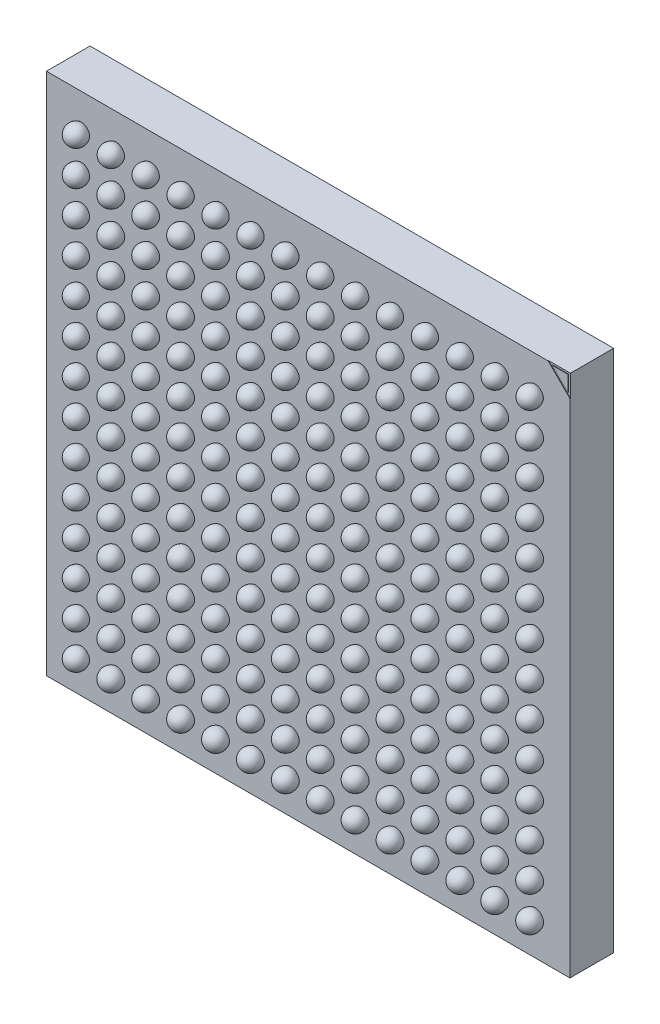
SolidWorks part; units mm, degrees
ref_plane "Front Plane" through (0, 0, 0) normal (0, 0, 1) x (1, 0, 0)
ref_plane "Top Plane" through (0, 0, 0) normal (0, 1, 0) x (1, 0, 0)
ref_plane "Right Plane" through (0, 0, 0) normal (1, 0, 0) x (0, 0, -1)
sketch "Sketch1" plane through (0, 0, 0) normal (0, 0, 1) x (1, 0, 0)
  line L1 (-6, 6) -> (6, 6)
  line L2 (-6, 6) -> (-6, -6)
  line L3 (-6, -6) -> (6, -6)
  line L4 (6, 6) -> (6, -6)
  line L5 (-6, 6) -> (6, -6) construction
  line L6 (-6, -6) -> (6, 6) construction
  point P0 (0, 0)
  dimension "D1" = 12
  dimension "D2" = 12
extrude "Boss-Extrude1" add sketch "Sketch1" along normal blind 1
sketch3d "3DSketch2" plane through (0, 0, 0) normal (0, 0, 1) x (1, 0, 0)
  dimension "D1" = 0.12
sketch3d "3DSketch1" plane through (0, 0, 0) normal (0, 0, 1) x (1, 0, 0)
  dimension "D1" = 0.01
sketch "Sketch3" plane through (0, 0, 1.12) normal (0, 0, 1) x (1, 0, 0)
  line L0 (-5.2, 5.425) -> (-5.2, 4.975)
  arc A0 (-5.2, 5.425) -> (-5.2, 4.975) centre (-5.2, 5.2) ccw
  dimension "D2" = 0.225
  dimension "D1" = 5.2
  dimension "D3" = 5.2
revolve "Revolve1" add sketch "Sketch3" angle 360 about L0
pattern_linear "LPattern1" count 14 spacing 0.8 along (1, 0, 0) of "Revolve1"
pattern_linear "LPattern2" count 14 spacing 0.8 along (0, -1, 0) of "Revolve1"
sketch "Sketch4" plane through (0, 0, 1) normal (0, 0, 1) x (1, 0, 0)
  line L0 (-6, -6) -> (6, 6) construction
sketch "Sketch5" plane through (0, 0, 1.12) normal (0, 0, 1) x (1, 0, 0)
  line L0 (5.2, 5.2) -> (5.2, -5.2) construction
  line L1 (-6, -6) -> (6, 6) construction
  line L2 (5.2, 4.63) -> (5.2, 4.17)
  arc A0 (5.2, 4.63) -> (5.2, 4.17) centre (5.2, 4.4) ccw
  dimension "D2" = 0.23
  dimension "D1" = 0.8
revolve "Revolve2" add sketch "Sketch5" angle 360 about L0
pattern_linear "LPattern3" count 12 spacing 0.8 along (0, -1, 0) of "Revolve2"
sketch "Sketch8" plane through (0, 0, 1.12) normal (0, 0, 1) x (1, 0, 0)
  line L0 (5.2, -4.9726) -> (5.2, -5.4326)
  line L1 (-5.2026, -5.2026) -> (6.4563, -5.2026) construction
  line L2 (-6, -6) -> (6, 6) construction
  line L3 (5.2, 5.2) -> (5.2, -5.8448) construction
  arc A0 (5.2, -4.9726) -> (5.2, -5.4326) centre (5.2, -5.2026) cw
  dimension "D2" = 0.23
  dimension "D1" = 0
  dimension "D3" = 0
revolve "Revolve3" add sketch "Sketch8" angle 360 about L0
pattern_linear "LPattern4" count 13 spacing 0.8 along (-1, 0, 0) of "Revolve3"
sketch "Sketch9" plane through (0, 0, 1.12) normal (0, 0, 1) x (1, 0, 0)
  line L0 (-5.2, 4.4) -> (-4.4, 4.4) construction
  line L1 (-4.4, 4.4) -> (-4.4, 5.2) construction
  line L2 (-4.4, 4.63) -> (-4.4, 4.17)
  arc A0 (-4.4, 4.63) -> (-4.4, 4.17) centre (-4.4, 4.4) cw
  dimension "D1" = 0.23
revolve "Revolve4" add sketch "Sketch9" angle 360 about L2
pattern_linear "LPattern5" count 12 spacing 0.8 along (1, 0, 0) of "Revolve4"
mirror "Mirror3" about plane through (0, 0, 0) normal (0, 1, 0) of "LPattern5", "Revolve4"
pattern_linear "LPattern6" count 11 spacing 0.8 along (0, -1, 0) of "Revolve4"
mirror "Mirror4" about plane through (0, 0, 0) normal (1, 0, 0) of "LPattern6"
sketch "Sketch10" plane through (0, 0, 1.12) normal (0, 0, 1) x (1, 0, 0)
  line L0 (-3.6, 4.4) -> (-3.6, 3.6) construction
  line L1 (-3.6, 3.6) -> (-4.4, 3.6) construction
  line L2 (-3.6, 3.83) -> (-3.6, 3.37)
  arc A0 (-3.6, 3.83) -> (-3.6, 3.37) centre (-3.6, 3.6) ccw
  circle A1 centre (-3.6, 4.4) radius 0.23 construction
  dimension "D1" = 0.23
  dimension "D4" = 0
  dimension "D2" = 0.8
  dimension "D3" = 0.8
revolve "Revolve5" add sketch "Sketch10" angle 360 about L2
pattern_linear "LPattern7" count 10 spacing 0.8 along (1, 0, 0) count 10 spacing 0.8 along (0, -1, 0) of "Revolve5"
sketch "Sketch11" plane through (0, 0, 0) normal (0, 0, -1) x (-1, 0, 0)
  line L0 (70.5838, 258.2384) -> (518.5838, 258.2384) construction
  line L1 (-4.3839, 0.8798) -> (-4.3839, 4.3103)
  line L2 (-4.3839, 4.3103) -> (-3.2934, 4.3103)
  line L3 (-3.2934, 4.3103) -> (-1.6992, 2.5075)
  line L4 (-1.6992, 2.5075) -> (-1.6992, 4.3103)
  line L5 (-1.6992, 4.3103) -> (-0.3405, 4.3103)
  line L6 (-0.3405, 4.3103) -> (0.2837, 3.3039)
  line L7 (0.2837, 3.3039) -> (0.9053, 4.3103)
  line L8 (0.9053, 4.3103) -> (3.9962, 4.3103)
  line L9 (4.5962, 3.7103) -> (4.5962, 2.7781)
  line L10 (3.9962, 2.1781) -> (2.3289, 2.1781)
  line L11 (2.3289, 2.1781) -> (2.3289, 0.8446)
  line L12 (2.3289, 0.8446) -> (0.9053, 0.8446)
  line L13 (0.9053, 0.8446) -> (0.2837, 1.8467)
  line L14 (0.2837, 1.8467) -> (-0.3243, 0.8623)
  line L15 (-0.3243, 0.8623) -> (-1.5859, 0.8623)
  line L16 (-1.5859, 0.8623) -> (-3.2198, 2.71)
  line L17 (-3.2198, 2.71) -> (-3.2198, 0.8798)
  line L18 (-3.2198, 0.8798) -> (-4.3839, 0.8798)
  line L19 (-4.2197, 1.0451) -> (-4.2197, 4.1148)
  line L20 (-4.2197, 4.1148) -> (-3.3227, 4.1148)
  line L21 (-3.3227, 4.1148) -> (-1.4957, 1.9924)
  line L22 (-1.4957, 1.9924) -> (-1.4957, 3.9002)
  line L23 (-1.4957, 3.9002) -> (-0.6806, 2.5941)
  line L24 (-0.6806, 2.5941) -> (-1.5943, 1.0735)
  line L25 (-1.5943, 1.0735) -> (-3.3751, 3.1423)
  line L26 (-3.3751, 3.1423) -> (-3.3751, 1.0451)
  line L27 (-3.3751, 1.0451) -> (-4.2197, 1.0451)
  line L28 (-1.4452, 4.1504) -> (-0.4308, 4.1504)
  line L29 (-0.4308, 4.1504) -> (0.2945, 2.9894)
  line L30 (0.2945, 2.9894) -> (0.9906, 4.1504)
  line L31 (0.9906, 4.1504) -> (2.0032, 4.1504)
  line L32 (2.0032, 4.1504) -> (1.0604, 2.5778)
  line L33 (1.0604, 2.5778) -> (2.0353, 1.0173)
  line L34 (2.0353, 1.0173) -> (1.0294, 1.0173)
  line L35 (1.0294, 1.0173) -> (0.2945, 2.1936)
  line L36 (0.2945, 2.1936) -> (-0.4046, 1.0274)
  line L37 (-0.4046, 1.0274) -> (-1.4452, 1.0274)
  line L38 (-1.4452, 1.0274) -> (-0.4588, 2.5941)
  line L39 (-0.4588, 2.5941) -> (-1.4452, 4.1504)
  line L40 (2.2198, 4.1504) -> (3.8592, 4.1274)
  line L41 (4.4508, 3.519) -> (4.4422, 2.907)
  line L42 (3.8422, 2.3154) -> (2.1526, 2.3154)
  line L43 (2.1526, 2.3154) -> (2.1526, 1.1096)
  line L44 (2.1526, 1.1096) -> (1.2674, 2.5778)
  line L45 (1.2674, 2.5778) -> (2.2198, 4.1504)
  line L46 (2.1526, 3.694) -> (3.7071, 3.694)
  line L47 (3.9071, 3.494) -> (3.9071, 2.9781)
  line L48 (3.7071, 2.7781) -> (2.1526, 2.7781)
  line L49 (2.1526, 3.694) -> (2.1526, 2.7781)
  line L50 (2.3133, 3.528) -> (3.5202, 3.528)
  line L51 (2.3133, 3.528) -> (2.3133, 2.9549)
  line L52 (2.3133, 2.9549) -> (3.5202, 2.9549)
  line L53 (3.7202, 3.328) -> (3.7202, 3.1549)
  arc A0 (4.5962, 2.7781) -> (3.9962, 2.1781) centre (3.9962, 2.7781) cw
  arc A1 (3.9962, 4.3103) -> (4.5962, 3.7103) centre (3.9962, 3.7103) cw
  arc A2 (4.4422, 2.907) -> (3.8422, 2.3154) centre (3.8422, 2.9154) cw
  arc A3 (3.8592, 4.1274) -> (4.4508, 3.519) centre (3.8508, 3.5274) cw
  arc A4 (3.5202, 2.9549) -> (3.7202, 3.1549) centre (3.5202, 3.1549) ccw
  arc A5 (3.5202, 3.528) -> (3.7202, 3.328) centre (3.5202, 3.328) cw
  arc A6 (3.9071, 2.9781) -> (3.7071, 2.7781) centre (3.7071, 2.9781) cw
  arc A7 (3.7071, 3.694) -> (3.9071, 3.494) centre (3.7071, 3.494) cw
extrude "Boss-Extrude2" add sketch "Sketch11" along normal blind 0.01 contours A1 L8 L7 L6 L5 L4 L3 L2 L1 L18 L17 L16 L15 L14 L13 L12 L11 L10 A0 L9 L38 L39 L28 L29 L30 L31 L32 L33 L34 L35 L36 L37 L26 L27 L19 L20 L21 L22 L23 L24 L25 L40 A3 L41 A2 L42 L43 L44 | A7 L46 L49 L48 A6 L47 L50 A5 L53 A4 L52 L51 region at (4.2876, 2.595, 0) region at (-2.9298, 3.6742, 0)
sketch "Sketch12" plane through (0, 0, 0) normal (0, 0, -1) x (-1, 0, 0)
  line L0 (-3.1438, -4.3314) -> (4.1393, -4.3314) construction
  text T0 "<b>SJA1110</b>" font "Century Gothic" height 1.2
extrude "Boss-Extrude3" add sketch "Sketch12" along normal blind 0.01
sketch "Sketch13" plane through (0, 0, 1) normal (0, 0, 1) x (1, 0, 0)
  line L0 (6, 6) -> (5.5, 6)
  line L1 (6, 6) -> (-6, 6) construction
  line L2 (5.5, 6) -> (6, 5.5)
  line L3 (6, -6) -> (6, 6) construction
  line L4 (6, 5.5) -> (6, 6)
  dimension "D1" = 0.5
  dimension "D2" = 0.5
extrude "Cut-Extrude1" cut sketch "Sketch13" against normal blind 0.01
sketch "Sketch14" plane through (0, 0, 0.99) normal (0, 0, 1) x (1, 0, 0)
  line L0 (5.5966, 5.96) -> (5.96, 5.96)
  line L1 (5.96, 5.96) -> (5.96, 5.6016)
  line L2 (5.96, 5.6016) -> (5.5966, 5.96)
  line L3 (6, 5.5) -> (6, 6) construction
  line L4 (6, 6) -> (5.5, 6) construction
  line L5 (5.5, 6) -> (6, 5.5) construction
  line L6 (5.5, 6) -> (6, 5.5) construction
  dimension "D1" = 0.04
  dimension "D2" = 0.04
  dimension "D3" = 0.04
  dimension "D4" = 0.0436
extrude "Boss-Extrude4" add sketch "Sketch14" along normal up to surface (0.01 mm away) up to face at (1.1, 1.1, 1)
